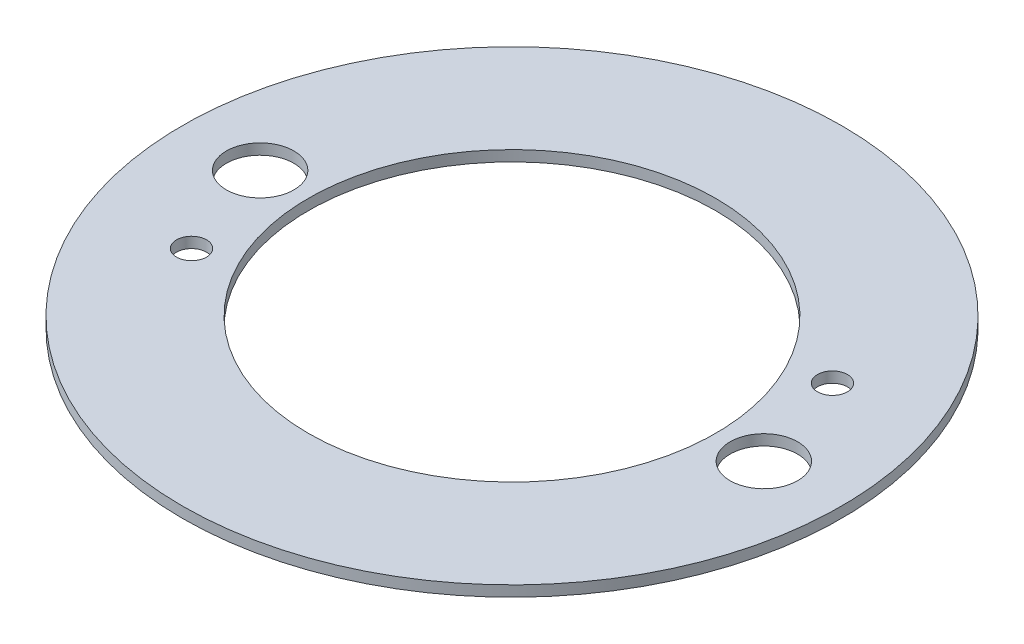
SolidWorks part; units mm, degrees
ref_plane "Front Plane" through (0, 0, 0) normal (0, 0, 1) x (1, 0, 0)
ref_plane "Top Plane" through (0, 0, 0) normal (0, 1, 0) x (1, 0, 0)
ref_plane "Right Plane" through (0, 0, 0) normal (1, 0, 0) x (0, 0, -1)
sketch "Sketch1" plane through (0, 0, 0) normal (0, 1, 0) x (1, 0, 0)
  circle A0 centre (0, 0) radius 78.105
  circle A1 centre (0, 0) radius 48.26
extrude "Boss-Extrude1" add sketch "Sketch1" along normal blind 2.54
sketch "Sketch2" plane through (0, 2.54, 0) normal (0, 1, 0) x (1, 0, 0)
  line L0 (59.69, 0) -> (-59.69, 0) construction
  line L1 (51.7955, 24.1526) -> (-51.7955, -24.1526) construction
  circle A0 centre (-59.69, 0) radius 8.001
  circle A1 centre (59.69, 0) radius 8.001
  circle A2 centre (-51.7955, -24.1526) radius 3.556
  circle A3 centre (51.7955, 24.1526) radius 3.556
  point P4 (0, 0)
  point P10 (0, 0)
extrude "Cut-Extrude1" cut sketch "Sketch2" against normal blind 2.54
